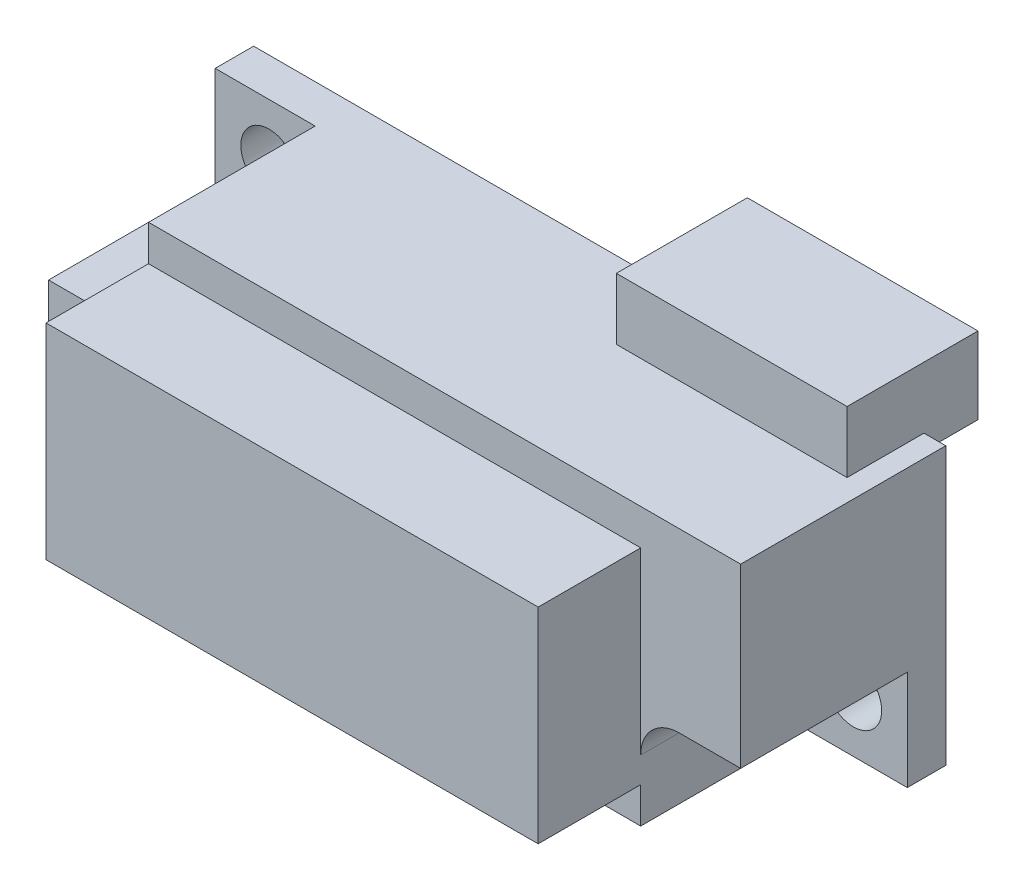
SolidWorks part; units mm, degrees
ref_plane "Front Plane" through (0, 0, 0) normal (0, 0, 1) x (1, 0, 0)
ref_plane "Top Plane" through (0, 0, 0) normal (0, 1, 0) x (1, 0, 0)
ref_plane "Right Plane" through (0, 0, 0) normal (1, 0, 0) x (0, 0, -1)
sketch "스케치1" plane through (0, 0, 0) normal (0, 0, 1) x (1, 0, 0)
  line L1 (-26.1453, 14.8512) -> (0.8547, 14.8512)
  line L2 (-26.1453, 14.8512) -> (-26.1453, 4.0512)
  line L3 (-26.1453, 4.0512) -> (0.8547, 4.0512)
  line L4 (0.8547, 14.8512) -> (0.8547, 4.0512)
  dimension "D1" = 27
  dimension "D2" = 10.8
extrude "보스-돌출1" add sketch "스케치1" along normal blind 12
sketch "스케치2" plane through (0, 0, 12) normal (0, 0, 1) x (1, 0, 0)
  line L0 (-3.0453, 6.6047) -> (-3.0453, -49993.3953) construction
  line L1 (-1.5019, 7.9512) -> (49998.4981, 7.9512) construction
  line L2 (-22.2453, 12.6216) -> (-22.2453, -49987.3784) construction
  line L3 (-26.1453, 10.9512) -> (49973.8547, 10.9512) construction
  line L5 (-26.1453, 14.8512) -> (-26.1453, 4.0512) construction
  line L6 (0.8547, 14.8512) -> (-26.1453, 14.8512) construction
  line L7 (0.8547, 4.0512) -> (0.8547, 14.8512) construction
  line L8 (-26.1453, 4.0512) -> (0.8547, 4.0512) construction
  line L10 (-26.1453, 14.8512) -> (-22.2453, 14.8512)
  line L11 (-26.1453, 14.8512) -> (-26.1453, 10.9512)
  line L12 (-26.1453, 10.9512) -> (-22.2453, 10.9512)
  line L13 (-22.2453, 14.8512) -> (-22.2453, 10.9512)
  line L14 (-3.0453, 7.9512) -> (0.8547, 7.9512)
  line L15 (-3.0453, 7.9512) -> (-3.0453, 4.0512)
  line L16 (-3.0453, 4.0512) -> (0.8547, 4.0512)
  line L17 (0.8547, 7.9512) -> (0.8547, 4.0512)
  dimension "D1" = 3.9
  dimension "D2" = 3.9
  dimension "D3" = 3.9
  dimension "D4" = 3.9
extrude "컷-돌출2" cut sketch "스케치2" against normal blind 10.5
fillet "필렛3" radius 1.5 1 edges at (-22.2453, 10.9512, 6.75)
fillet "필렛4" radius 1.5 1 edges at (-3.0453, 7.9512, 6.75)
sketch "스케치3" plane through (0, 0, 1.5) normal (0, 0, 1) x (1, 0, 0)
  line L0 (-24.0453, 12.9454) -> (-24.0453, -49987.0546) construction
  line L1 (-24.6521, 12.7512) -> (49975.3479, 12.7512) construction
  line L2 (-1.2453, 5.9301) -> (-1.2453, -49994.0699) construction
  line L3 (-1.9605, 6.1512) -> (49998.0395, 6.1512) construction
  line L5 (-26.1453, 14.8512) -> (-26.1453, 10.9512) construction
  line L6 (-22.2453, 14.8512) -> (-26.1453, 14.8512) construction
  line L7 (-3.0453, 4.0512) -> (0.8547, 4.0512) construction
  line L8 (0.8547, 4.0512) -> (0.8547, 7.9512) construction
  circle A0 centre (-24.0453, 12.7512) radius 1.1
  circle A1 centre (-1.2453, 6.1512) radius 1.1
  dimension "D1" = 2.1
  dimension "D2" = 2.1
  dimension "D3" = 2.1
  dimension "D4" = 2.1
extrude "컷-돌출3" cut sketch "스케치3" against normal blind 10.5
sketch "스케치4" plane through (0, 0, 12) normal (0, 0, 1) x (1, 0, 0)
  line L0 (0.8547, 7.9512) -> (0.8547, 14.8512) construction
  line L1 (-22.2453, 13.4512) -> (-3.0453, 13.4512)
  line L2 (-22.2453, 13.4512) -> (-22.2453, 5.4512)
  line L3 (-22.2453, 5.4512) -> (-3.0453, 5.4512)
  line L4 (-3.0453, 13.4512) -> (-3.0453, 5.4512)
  line L5 (-26.1453, 4.0512) -> (-3.0453, 4.0512) construction
  line L7 (-26.1453, 14.8512) -> (0.8547, 14.8512)
  line L8 (-26.1453, 14.8512) -> (-26.1453, 4.0512)
  line L9 (-26.1453, 4.0512) -> (0.8547, 4.0512)
  line L10 (0.8547, 14.8512) -> (0.8547, 4.0512)
  dimension "D1" = 8
  dimension "D2" = 19.2
  dimension "D3" = 3.9
  dimension "D4" = 1.4
extrude "컷-돌출4" cut sketch "스케치4" against normal blind 4
sketch "스케치5" plane through (0, 0, 0) normal (0, 0, -1) x (-1, 0, 0)
  line L0 (26.1453, 4.0512) -> (-0.8547, 4.0512) construction
  line L1 (-0.0047, 17.2512) -> (8.9953, 17.2512)
  line L2 (-0.0047, 17.2512) -> (-0.0047, 14.2512)
  line L3 (-0.0047, 14.2512) -> (8.9953, 14.2512)
  line L4 (8.9953, 17.2512) -> (8.9953, 14.2512)
  line L5 (-0.8547, 4.0512) -> (-0.8547, 14.8512) construction
  dimension "D1" = 13.2
  dimension "D2" = 3
  dimension "D3" = 9
  dimension "D4" = 9.85
extrude "보스-돌출2" add sketch "스케치5" along normal blind 2.108 and the other way blind 3
